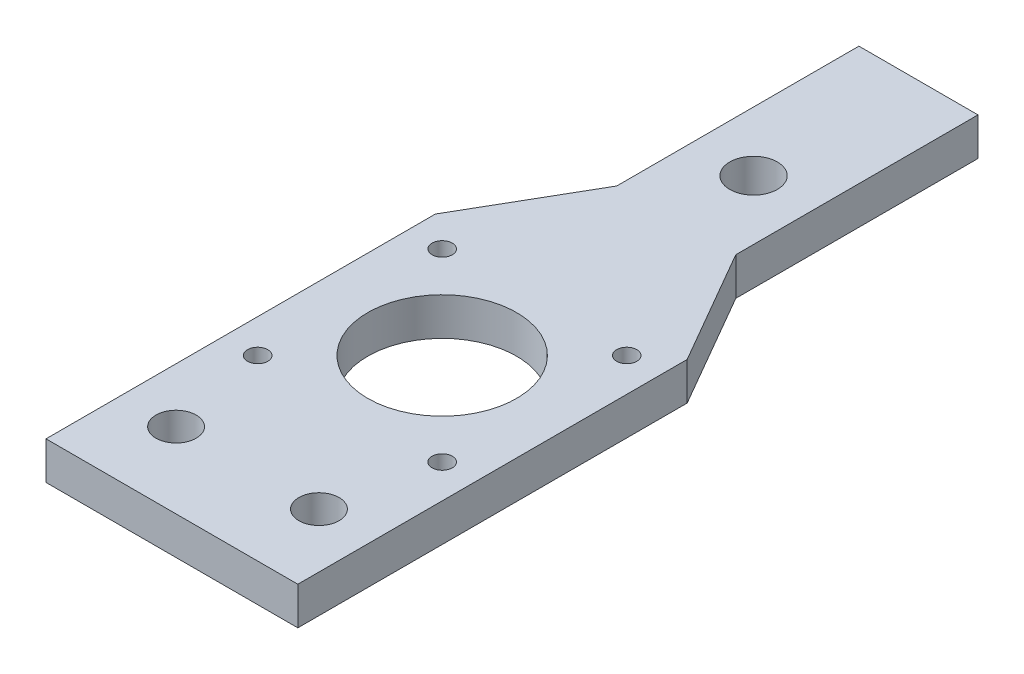
SolidWorks part; units mm, degrees
ref_plane "Front Plane" through (0, 0, 0) normal (0, 0, 1) x (1, 0, 0)
ref_plane "Top Plane" through (0, 0, 0) normal (0, 1, 0) x (1, 0, 0)
ref_plane "Right Plane" through (0, 0, 0) normal (1, 0, 0) x (0, 0, -1)
sketch "Sketch2" plane through (0, 0, 0) normal (0, 1, 0) x (1, 0, 0)
  line L0 (10, 0) -> (10, -100) construction
  line L1 (0, 0) -> (20, 0)
  line L2 (0, 0) -> (0, -100)
  line L3 (0, -100) -> (20, -100)
  line L4 (20, 0) -> (20, -100)
  line L5 (-11.15, -60) -> (0, -40.6876)
  line L6 (-11.15, -100) -> (31.15, -100)
  line L7 (-11.15, -100) -> (-11.15, -60)
  line L8 (-11.15, -60) -> (31.15, -60)
  line L9 (31.15, -100) -> (31.15, -60)
  line L10 (-11.15, -100) -> (31.15, -60) construction
  line L11 (-11.15, -60) -> (31.15, -100) construction
  line L12 (20, -40.6876) -> (31.15, -60)
  circle A0 centre (10, -80) radius 12.5
  circle A1 centre (10, -27.7) radius 4
  dimension "D3" = 8
  dimension "D4" = 25
  dimension "D1" = 100
  dimension "D2" = 20
  dimension "D5" = 52.3
  dimension "D6" = 20
  dimension "D8" = 42.3
  dimension "D9" = 60
  dimension "D10" = 60
extrude "Boss-Extrude1" add sketch "Sketch2" along normal blind 6.35 contours L2 L8 L4 L1 A1 | L5 L8 L2 | L12 L4 L8 | A0 L4 L8 L2 | A0 L2 L3 L4 | A0 L2 L8 L7 L6 | A0 L4 L6 L9 L8 region at (10, 0, 0.6325) region at (-3.7167, 0, 53.5625) region at (23.7167, 0, 53.5625) region at (10, 0, 64.6159) region at (-5.8524, 0, 80) region at (25.8524, 0, 80) region at (10, 0, 95.3841)
sketch "Sketch3" plane through (0, 6.35, 0) normal (0, 1, 0) x (1, 0, 0)
  line L1 (-5.5, -95.5) -> (25.5, -95.5) construction
  line L2 (-5.5, -95.5) -> (-5.5, -64.5) construction
  line L3 (-5.5, -64.5) -> (25.5, -64.5) construction
  line L4 (25.5, -95.5) -> (25.5, -64.5) construction
  line L5 (-5.5, -95.5) -> (25.5, -64.5) construction
  line L6 (-5.5, -64.5) -> (25.5, -95.5) construction
  point P0 (10, -80)
  dimension "D1" = 31
hole_wizard "M3 Clearance Hole1" positions "Sketch4" profile "Sketch5" hole size "M3" standard "ANSI Metric" end condition through all
sketch "Sketch4" plane through (0, 6.35, 0) normal (0, 1, 0) x (1, 0, 0)
  point P0 (-5.5, -64.5)
  point P3 (25.5, -64.5)
  point P6 (25.5, -95.5)
  point P9 (-5.5, -95.5)
sketch "Sketch5" plane through (-5.5, 6.35, 64.5) normal (1, 0, 0) x (0, 0, 1)
  line L0 (0, 0) -> (0, 6.35)
  line L1 (0, 6.35) -> (1.7, 6.35)
  line L2 (1.7, 6.35) -> (1.7, 0)
  line L5 (1.7, 0) -> (0, 0)
  line L11 (0, -6.35) -> (0, 107.95) construction
  dimension "Thru Hole Dia." = 3.4
  dimension "Thru Hole Depth" = 6.35
sketch "Sketch7" plane through (0, 6.35, 0) normal (0, 1, 0) x (1, 0, 0)
  line L1 (-11.15, -100) -> (31.15, -100)
  line L2 (-11.15, -100) -> (-11.15, -125.4)
  line L3 (-11.15, -125.4) -> (31.15, -125.4)
  line L4 (31.15, -100) -> (31.15, -125.4)
  line L5 (-11.15, -100) -> (-11.15, -60) construction
  dimension "D1" = 25.4
extrude "Boss-Extrude2" add sketch "Sketch7" against normal up to surface (6.35 mm away) up to face at (-5.5, 0, 66.2)
sketch "Sketch8" plane through (0, 6.35, 0) normal (0, 1, 0) x (1, 0, 0)
  line L0 (10, -125.4) -> (10, -112.7) construction
  line L1 (-11.15, -125.4) -> (31.15, -125.4) construction
  line L2 (-2, -112.7) -> (22, -112.7) construction
  point P7 (10, -112.7)
  dimension "D1" = 12.7
  dimension "D2" = 24
hole_wizard "1/4 Clearance Hole1" positions "Sketch9" profile "Sketch10" hole size "1/4" standard "ANSI Inch" end condition through all
sketch "Sketch9" plane through (0, 6.35, 0) normal (0, 1, 0) x (1, 0, 0)
  point P0 (-2, -112.7)
  point P3 (22, -112.7)
sketch "Sketch10" plane through (-2, 6.35, 112.7) normal (1, 0, 0) x (0, 0, 1)
  line L0 (0, 0) -> (0, 6.35)
  line L1 (0, 6.35) -> (3.3782, 6.35)
  line L2 (3.3782, 6.35) -> (3.3782, 0)
  line L5 (3.3782, 0) -> (0, 0)
  line L11 (0, -6.35) -> (0, 107.95) construction
  dimension "Thru Hole Dia." = 6.7564
  dimension "Thru Hole Depth" = 6.35
